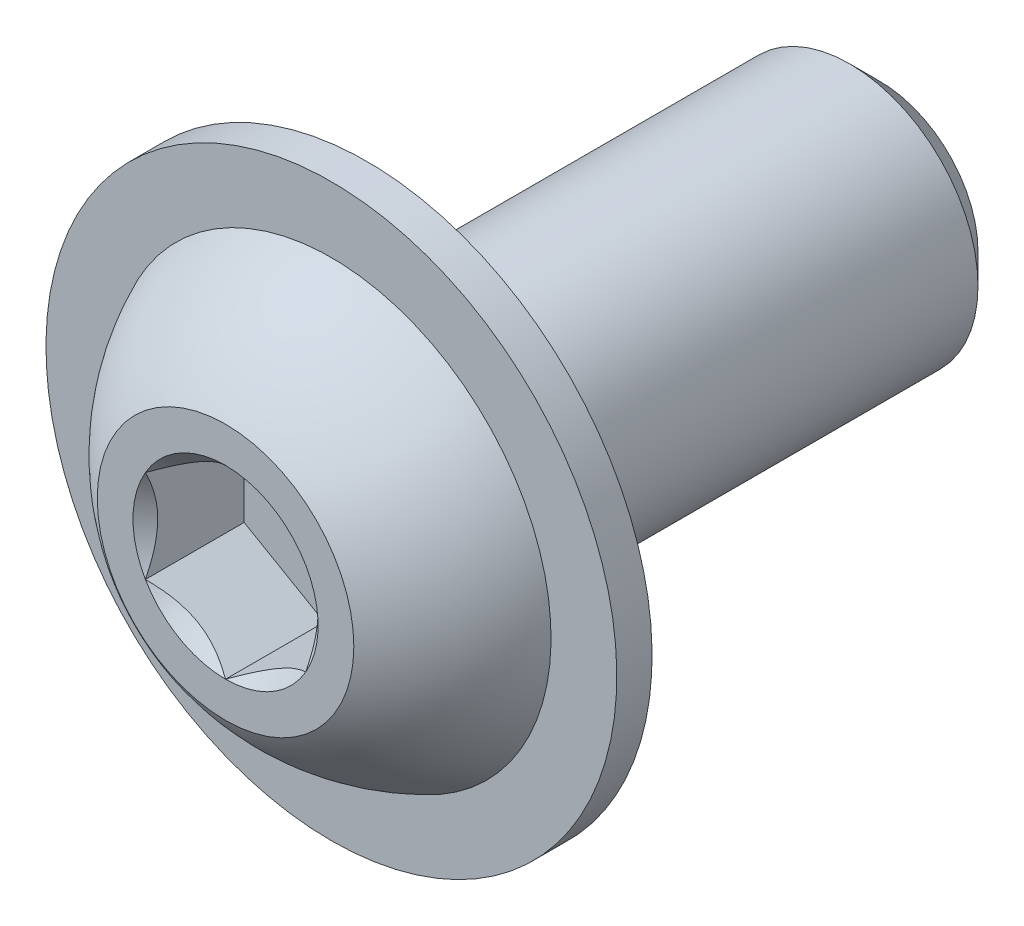
SolidWorks part; units mm, degrees
ref_plane "Front" through (0, 0, 0) normal (0, 0, 1) x (1, 0, 0)
ref_plane "Top" through (0, 0, 0) normal (0, 1, 0) x (1, 0, 0)
ref_plane "Right" through (0, 0, 0) normal (1, 0, 0) x (0, 0, -1)
sketch "Sketch1" plane through (0, 0, 0) normal (1, 0, 0) x (0, 0, -1)
  line L2 (-5.8, 4) -> (10.2, 4)
  line L3 (10.2, 4) -> (10.2, 0)
  line L4 (10.2, -4) -> (8.95, -4) construction
  line L6 (-6.9, 6.85) -> (-5.8, 6.85) construction
  line L7 (10.2, 4) -> (10.2, -4) construction
  line L8 (-10.2, 0) -> (10.2, 0) construction
  line L9 (-5.8, 6.85) -> (-5.8, -6.85) construction
  line L11 (-5.8, 4) -> (-5.8, 0)
  line L13 (-10.2, 2.5) -> (-10.2, -2.5) construction
  line L14 (-10.2, 2.5) -> (-10.2, 4) construction
  line L15 (-6.9, 6.85) -> (-6.9, 8.9) construction
  line L16 (-6.9, 8.9) -> (-5.8, 8.9) construction
  line L17 (-5.8, 8.9) -> (-5.8, 6.85) construction
  line L18 (-5.8, 8.9) -> (-5.8, -8.9) construction
  arc A3 (-10.2, 4) -> (-6.9, 6.85) centre (-3.8648, 0) cw construction
  point P16 (5.825, -4)
  point P24 (0, 0)
  dimension "Thread OD" = 8
  dimension "D1" = 1.1
  dimension "Head Height" = 4.4
  dimension "Head Diameter" = 13.7
  dimension "Length" = 16
  dimension "Drive Size" = 5
  dimension "Flange Diameter" = 17.8
  dimension "D2" = 4.375
  dimension "Thread Pitch" = 1.25
sketch "Sketch13" plane through (0, 0, 0) normal (1, 0, 0) x (0, 0, -1)
  line L1 (-5.8, 4) -> (10.2, 4)
  line L2 (-5.8, 4) -> (-5.8, 0)
  line L3 (-5.8, 0) -> (10.2, 0)
  line L4 (10.2, 4) -> (10.2, 0)
revolve "Revolve1" add sketch "Sketch13" angle 360 about L8
chamfer "Chamfer1" distance 0.9375 angle 45 1 edges at (4, 0, -10.2)
sketch "Sketch7" plane through (0, 0, 0) normal (1, 0, 0) x (0, 0, -1)
  line L0 (-5.8, 6.85) -> (-5.8, -6.85) construction
  line L1 (-5.8, 6.85) -> (-5.8, 0)
  line L2 (-6.9, 6.85) -> (-6.9, 8.9)
  line L3 (-6.9, 8.9) -> (-5.8, 8.9)
  line L4 (-5.8, 8.9) -> (-5.8, 6.85)
  line L6 (-6.9, 6.85) -> (-5.8, 6.85) construction
  line L8 (-10.2, 0) -> (10.2, 0) construction
  line L12 (-6.9, 6.85) -> (-5.8, 6.85) construction
  line L13 (-10.2, 0) -> (-5.8, 0)
  line L14 (-10.2, 2.5) -> (-10.2, -2.5) construction
  line L16 (-10.2, 4) -> (-10.2, 0)
  arc A2 (-6.9, 6.85) -> (-10.2, 4) centre (-3.8648, 0) ccw construction
  arc A3 (-6.9, 6.85) -> (-10.2, 4) centre (-3.8648, 0) ccw
revolve "Revolve2" add sketch "Sketch7" angle 360 mid plane about L13
sketch "Sketch5" plane through (0, 0, 10.2) normal (0, 0, 1) x (1, 0, 0)
  line L1 (2.5, -1.4434) -> (2.5, 1.4434)
  line L2 (2.5, 1.4434) -> (0, 2.8868)
  line L3 (0, 2.8868) -> (-2.5, 1.4434)
  line L4 (-2.5, 1.4434) -> (-2.5, -1.4434)
  line L5 (-2.5, -1.4434) -> (0, -2.8868)
  line L6 (0, -2.8868) -> (2.5, -1.4434)
  circle A0 centre (0, 0) radius 2.5 construction
extrude "Cut-Extrude2" cut sketch "Sketch5" against normal blind 3.08
sketch "Sketch6" plane through (0, 0, 10.2) normal (0, 0, 1) x (1, 0, 0)
  circle A0 centre (0, 0) radius 2.8868
extrude "Cut-Extrude3" cut sketch "Sketch6" against normal blind 3.08 draft 45
split "Split1" [suppressed] bodies to split 113
sketch "Sketch14" [suppressed] plane through (0, 0, -10.2) normal (0, 0, -1) x (-1, 0, 0)
  circle A0 centre (0, 0) radius 4 construction
  circle A1 centre (0, 0) radius 4
curve "Helix/Spiral1" [suppressed] pitch 1.25 height 17.25 turns 13.8
sketch "Sketch16" [suppressed] plane through (0, 0, 0) normal (1, 0, 0) x (0, 0, -1)
  line L0 (11.3719, 4.1353) -> (10.1219, 4.1353) construction
  line L1 (10.1219, 4.1353) -> (10.7469, 3.0528) construction
  line L2 (10.7469, 3.0528) -> (11.3719, 4.1353) construction
  line L3 (11.2937, 4) -> (10.2, 4) construction
  line L4 (10.7469, 4.1353) -> (10.7469, 4) construction
  line L5 (11.3328, 4.0677) -> (10.1609, 4.0677) construction
  line L6 (10.825, 3.1881) -> (10.6687, 3.1881) construction
  line L7 (10.7469, 3.1881) -> (10.7469, 3.0528) construction
  line L8 (10.6687, 3.1881) -> (10.1609, 4.0677)
  line L9 (10.1609, 4.0677) -> (11.3328, 4.0677)
  line L10 (11.3328, 4.0677) -> (10.825, 3.1881)
  line L11 (10.825, 3.1881) -> (10.6687, 3.1881)
  point P11 (10.7469, 4.0677)
  dimension "D1" = 1.25
  dimension "D2" = 0.1562
sweep "Cut-Sweep1" [suppressed] cut profiles "Sketch16" path "Helix/Spiral1"
sketch "Sketch17" [suppressed] plane through (0, 0, 5.8) normal (0, 0, -1) x (-1, 0, 0)
  circle A1 centre (0, 0) radius 4
  circle A2 centre (0, 0) radius 4
  dimension "D1" = 0
extrude "Boss-Extrude1" [suppressed] add sketch "Sketch17" along normal up to next draft 20
equation "\"D3@Helix/Spiral1\" = \"Length@Sketch1\" + \"D4@Helix/Spiral1\""
equation "\"D1@Chamfer1\" = \"D4@Helix/Spiral1\" * .75"
equation "\"D1@Cut-Extrude2\" = \"Head Height@Sketch1\" * .7"
equation "\"D1@Sketch1\" = \"Head Height@Sketch1\" * .25"
equation "\"D1@Cut-Extrude3\" = \"D1@Cut-Extrude2\""
equation "\"D2@Sketch1\"=\"D4@Helix/Spiral1\"*3.5"
equation "\"D4@Helix/Spiral1\"=\"Thread Pitch@Sketch1\""
equation "\"D1@Sketch16\"=\"Thread Pitch@Sketch1\""
equation "\"D2@Sketch16\"=\"D1@Sketch16\"/8"
